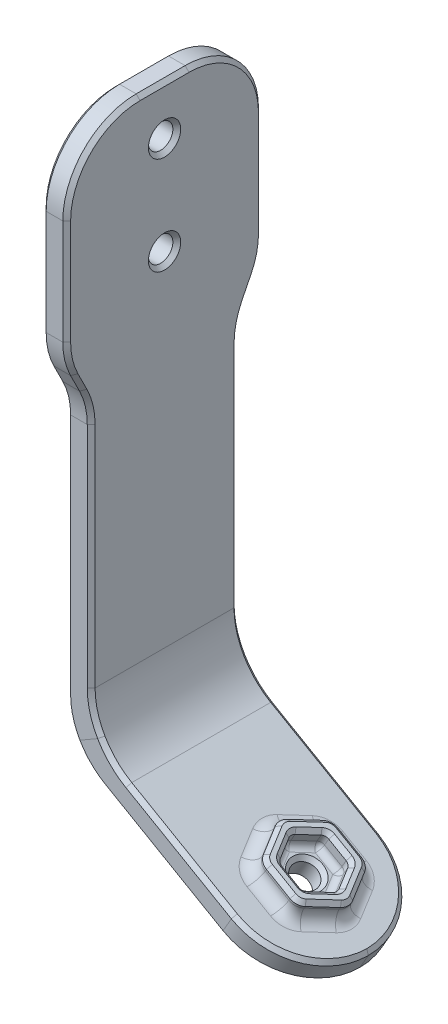
SolidWorks part; units mm, degrees
ref_plane "Front Plane" through (0, 0, 0) normal (0, 0, 1) x (1, 0, 0)
ref_plane "Top Plane" through (0, 0, 0) normal (0, 1, 0) x (1, 0, 0)
ref_plane "Right Plane" through (0, 0, 0) normal (1, 0, 0) x (0, 0, -1)
sketch "Sketch1" plane through (0, 0, 0) normal (0, 0, 1) x (1, 0, 0)
  line L0 (0, 0) -> (0, -31.75)
  line L1 (0, -31.75) -> (0, -70.0334)
  line L2 (0, -70.0334) -> (27.4963, -85.9084)
  dimension "D1" = 31.75
  dimension "D2" = 38.2834
  dimension "D3" = 180
  dimension "D4" = 120
  dimension "D5" = 31.75
sketch "Sketch2" plane through (0, 0, 0) normal (0, 1, 0) x (1, 0, 0)
  line L1 (-1.5875, -9.525) -> (1.5875, -9.525)
  line L2 (-1.5875, -9.525) -> (-1.5875, 9.525)
  line L3 (-1.5875, 9.525) -> (1.5875, 9.525)
  line L4 (1.5875, -9.525) -> (1.5875, 9.525)
  line L5 (-1.5875, -9.525) -> (1.5875, 9.525) construction
  line L6 (-1.5875, 9.525) -> (1.5875, -9.525) construction
  point P0 (0, 0)
  dimension "D1" = 3.175
  dimension "D2" = 19.05
sweep "Sweep1" add profiles "Sketch2" path "Sketch1"
sketch "Sketch4" plane through (-1.5875, 0, 0) normal (-1, 0, 0) x (0, 0, 1)
  line L0 (-12.7, -25.4) -> (-9.525, -31.75)
  line L1 (-12.7, 0) -> (12.7, 0)
  line L2 (-12.7, 0) -> (-12.7, -25.4)
  line L3 (-12.7, -25.4) -> (12.7, -25.4) construction
  line L4 (12.7, 0) -> (12.7, -25.4)
  line L5 (-9.525, 0) -> (-9.525, -31.75) construction
  line L6 (-9.525, -31.75) -> (9.525, -31.75)
  line L7 (9.525, 0) -> (9.525, -31.75) construction
  line L8 (9.525, -31.75) -> (12.7, -25.4)
  point P4 (0, 0)
  dimension "D1" = 25.4
  dimension "D2" = 6.35
  dimension "D3" = 25.4
extrude "Boss-Extrude1" add sketch "Sketch4" against normal up to surface (3.175 mm away) up to face at (1.5875, -15.875, 0)
sketch "Sketch3" plane through (-1.5875, 0, 0) normal (-1, 0, 0) x (0, 0, 1)
  line L0 (0, -19.05) -> (0, -6.35) construction
  line L1 (0, -6.35) -> (0, 0) construction
  circle A0 centre (0, -6.35) radius 1.5875
  circle A1 centre (0, -19.05) radius 1.5875
  dimension "D1" = 3.175
  dimension "D2" = 6.35
  dimension "D3" = 12.7
extrude "Cut-Extrude1" cut sketch "Sketch3" against normal up to next
sketch "Sketch5" plane through (-29.5316, -51.1502, 0) normal (0.5, 0.866, 0) x (0.866, -0.5, 0)
  line L0 (57.2417, 0) -> (66.7667, 0) construction
  line L1 (66.7667, -9.525) -> (66.7667, 9.525) construction
  circle A0 centre (57.2417, 0) radius 1.5875
  dimension "D1" = 3.175
  dimension "D2" = 9.525
extrude "Cut-Extrude2" cut sketch "Sketch5" against normal up to next
sketch "Sketch6" plane through (-29.5316, -51.1502, 0) normal (0.5, 0.866, 0) x (0.866, -0.5, 0)
  line L1 (59.0015, 3.048) -> (55.4819, 3.048)
  line L2 (55.4819, 3.048) -> (53.7222, 0)
  line L3 (53.7222, 0) -> (55.4819, -3.048)
  line L4 (55.4819, -3.048) -> (59.0015, -3.048)
  line L5 (59.0015, -3.048) -> (60.7612, 0)
  line L6 (60.7612, 0) -> (59.0015, 3.048)
  line L7 (59.918, 4.6355) -> (54.5654, 4.6355)
  line L8 (54.5654, 4.6355) -> (51.8891, 0)
  line L9 (51.8891, 0) -> (54.5654, -4.6355)
  line L10 (54.5654, -4.6355) -> (59.918, -4.6355)
  line L11 (59.918, -4.6355) -> (62.5943, 0)
  line L12 (62.5943, 0) -> (59.918, 4.6355)
  circle A0 centre (57.2417, 0) radius 3.048 construction
  circle A1 centre (57.2417, 0) radius 4.6355 construction
  dimension "D1" = 6.096
  dimension "D2" = 1.5875
extrude "Boss-Extrude2" add sketch "Sketch6" along normal blind 2.3813
fillet "Fillet1" radius 9.525 2 edges at (27.4963, -85.9084, -9.525) (27.4963, -85.9084, 9.525)
fillet "Fillet2" radius 9.525 2 edges at (-1.5875, -70.95, 0) (1.5875, -69.1169, 0)
fillet "Fillet3" radius 9.525 6 edges at (0, 0, -12.7) (0, 0, 12.7) (0, -25.4, -12.7) (0, -31.75, -9.525) (0, -25.4, 12.7) (0, -31.75, 9.525)
fillet "Fillet4" radius 1.5875 12 edges at (25.272, -81.4163, 0) (16.001, -76.0637, 0) (18.3187, -77.4018, -4.6355) (22.9542, -80.0781, -4.6355) (18.3187, -77.4018, 4.6355) (22.9542, -80.0781, 4.6355) (20.0412, -79.7711, -4.6355) (16.5645, -77.7639, -2.3178) (16.5645, -77.7639, 2.3178) (20.0412, -79.7711, 4.6355) (23.5178, -81.7783, -2.3178) (23.5178, -81.7783, 2.3178)
fillet "Fillet5" radius 0.7937 12 edges at (20.0412, -79.7711, 3.048) (17.7552, -78.4513, 1.524) (20.0412, -79.7711, -3.048) (22.3272, -81.0909, -1.524) (22.3272, -81.0909, 1.524) (17.7552, -78.4513, -1.524) (17.5885, -76.9802, 0) (19.1125, -77.8601, 3.048) (22.1605, -79.6199, 3.048) (23.6845, -80.4998, 0) (22.1605, -79.6199, -3.048) (19.1125, -77.8601, -3.048)
chamfer "Chamfer1" distance 0.508 angle 45 72 edges at (19.761, -76.8597, -2.9417) (18.9458, -76.3891, -1.524) (18.2901, -76.0105, 0) (18.9458, -76.3891, 1.524) (19.761, -76.8597, 2.9417) (21.2318, -77.7089, 3.048) (22.7026, -78.5581, 2.9417) (23.5178, -79.0287, 1.524) (24.1734, -79.4072, 0) (23.5178, -79.0287, -1.524) (22.7026, -78.5581, -2.9417) (21.2318, -77.7089, -3.048) (23.4432, -78.9856, 4.4228) (21.2318, -77.7089, 4.6355) (19.0204, -76.4321, 4.4228) (17.7552, -75.7016, 2.3178) (16.809, -75.1554, 0) (17.7552, -75.7016, -2.3178) (19.0204, -76.4321, -4.4228) (21.2318, -77.7089, -4.6355) (23.4432, -78.9856, -4.4228) (24.7084, -79.7161, -2.3177) (25.6546, -80.2624, 0) (24.7084, -79.7161, 2.3178) (17.0788, -81.727, 0) (18.6663, -78.9773, 0) (1.5875, -7.9375, 0) (-1.5875, -7.9375, 0) (1.5875, -20.6375, 0) (-1.5875, -20.6375, 0) (-1.5875, -28.575, -11.1125) (1.5875, -28.575, -11.1125) (1.5875, -31.8102, -9.7798) (1.5875, -25.3398, -12.4452) (1.5875, -48.8081, -9.525) (-1.5875, -16.3382, -12.7) (1.5875, -16.3382, -12.7) (1.9121, -66.0829, -9.525) (1.5875, -2.7898, -9.9102) (4.3773, -70.3528, -9.525) (1.5875, 0, 0) (13.1956, -75.8188, -9.525) (1.5875, -2.7898, 9.9102) (25.874, -83.1387, -6.7352) (1.5875, -16.3382, 12.7) (-1.5875, -16.3382, 12.7) (25.874, -83.1387, 6.7352) (1.5875, -25.3398, 12.4452) (13.1956, -75.8188, 9.525) (1.5875, -28.575, 11.1125) (-1.5875, -28.575, 11.1125) (4.3773, -70.3528, 9.525) (1.5875, -31.8102, 9.7798) (1.9121, -66.0829, 9.525) (1.5875, -48.8081, 9.525) (-1.5875, -31.8102, -9.7798) (-1.5875, -25.3398, -12.4452) (-1.5875, -49.7246, -9.525) (-1.2629, -67.9159, -9.525) (-1.5875, -2.7898, -9.9102) (1.2023, -72.1859, -9.525) (-1.5875, 0, 0) (10.8143, -78.1102, -9.525) (-1.5875, -2.7898, 9.9102) (24.2865, -85.8883, -6.7352) (24.2865, -85.8883, 6.7352) (-1.5875, -25.3398, 12.4452) (10.8143, -78.1102, 9.525) (1.2023, -72.1859, 9.525) (-1.5875, -31.8102, 9.7798) (-1.2629, -67.9159, 9.525) (-1.5875, -49.7246, 9.525)
equation "\"D2@Sketch1\"=0.75+0.40625+0.350971"
